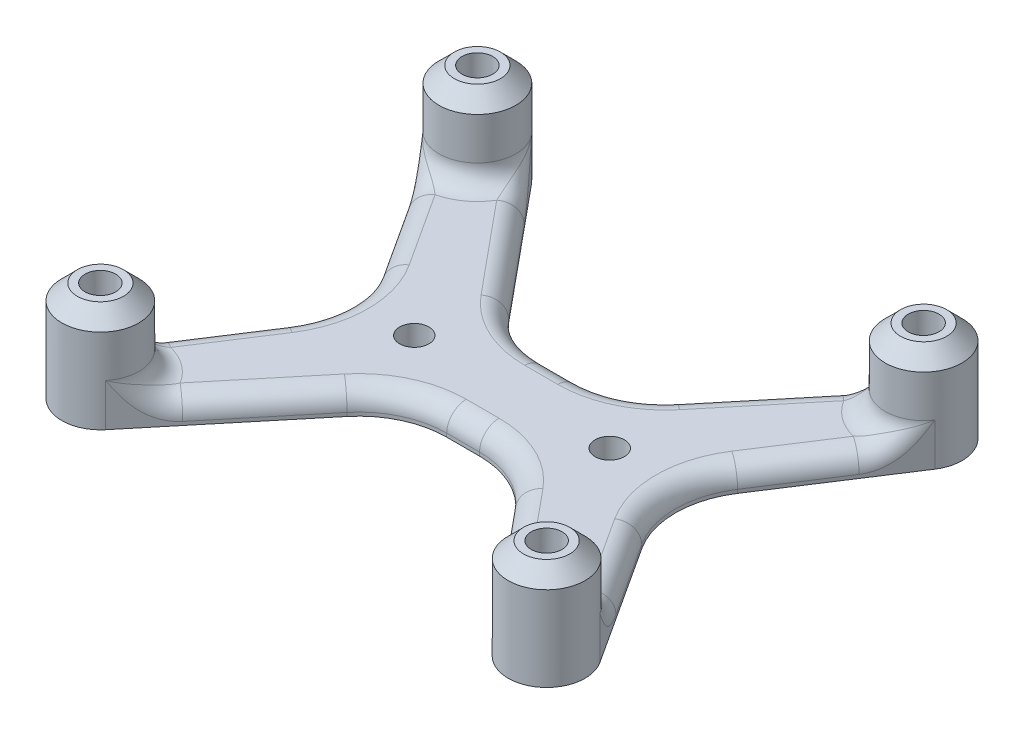
SolidWorks part; units mm, degrees
ref_plane "Front Plane" through (0, 0, 0) normal (0, 0, 1) x (1, 0, 0)
ref_plane "Top Plane" through (0, 0, 0) normal (0, 1, 0) x (1, 0, 0)
ref_plane "Right Plane" through (0, 0, 0) normal (1, 0, 0) x (0, 0, -1)
sketch "Sketch1" plane through (0, 0, 0) normal (0, 1, 0) x (1, 0, 0)
  line L0 (-7.5163, 6.35) -> (7.5163, 6.35)
  line L1 (-29, -24.5) -> (29, -24.5) construction
  line L2 (-29, -24.5) -> (-29, 24.5) construction
  line L3 (-29, 24.5) -> (29, 24.5) construction
  line L4 (29, -24.5) -> (29, 24.5) construction
  line L5 (-29, -24.5) -> (29, 24.5) construction
  line L6 (-29, 24.5) -> (29, -24.5) construction
  line L7 (-19.05, -6.35) -> (19.05, -6.35) construction
  line L8 (-19.05, -6.35) -> (-19.05, 6.35) construction
  line L9 (-19.05, 6.35) -> (19.05, 6.35) construction
  line L10 (19.05, -6.35) -> (19.05, 6.35) construction
  line L11 (-19.05, -6.35) -> (19.05, 6.35) construction
  line L12 (-19.05, 6.35) -> (19.05, -6.35) construction
  line L13 (7.5163, 6.35) -> (25.1456, 27.6849)
  line L14 (19.05, 0) -> (33.1932, 21.7766)
  line L15 (19.05, 0) -> (33.1932, -21.7766)
  line L16 (25.1456, -27.6849) -> (7.5163, -6.35)
  line L17 (7.5163, -6.35) -> (-7.5163, -6.35)
  line L18 (-7.5163, -6.35) -> (-25.1456, -27.6849)
  line L19 (-19.05, 0) -> (-33.1932, -21.7766)
  line L20 (-19.05, 0) -> (-33.1932, 21.7766)
  line L21 (-25.1456, 27.6849) -> (-7.5163, 6.35)
  circle A0 centre (-29, -24.5) radius 5
  circle A1 centre (29, -24.5) radius 5
  circle A2 centre (29, 24.5) radius 5
  circle A3 centre (-29, 24.5) radius 5
  point P0 (0, 0)
  point P6 (0, 0)
  dimension "D5" = 10
  dimension "D6" = 10
  dimension "D7" = 10
  dimension "D8" = 10
  dimension "D1" = 12.7
  dimension "D2" = 38.1
  dimension "D3" = 58
  dimension "D4" = 49
extrude "Boss-Extrude1" add sketch "Sketch1" along normal blind 3 contours A0 | A3 L20 L19 A0 L18 L17 L16 A1 L15 L14 A2 L13 L0 L21 | A3 | A2 | A1 region at (0, 0, 0) region at (-29, 0, -24.5) region at (29, 0, -24.5) region at (-29, 0, 24.5) region at (29, 0, 24.5)
sketch "Sketch2" plane through (0, 3, 0) normal (0, 1, 0) x (1, 0, 0)
  circle A0 centre (-29, -24.5) radius 5
  circle A1 centre (29, -24.5) radius 5
  circle A2 centre (29, 24.5) radius 5
  circle A3 centre (-29, 24.5) radius 5
extrude "Boss-Extrude2" add sketch "Sketch2" along normal blind 10
sketch "Sketch3" plane through (0, 13, 0) normal (0, 1, 0) x (1, 0, 0)
  circle A0 centre (-29, -24.5) radius 2
  circle A1 centre (-29, 24.5) radius 2
  circle A2 centre (29, 24.5) radius 2
  circle A3 centre (29, -24.5) radius 2
  dimension "D1" = 4
  dimension "D2" = 4
  dimension "D3" = 4
  dimension "D4" = 4
extrude "Cut-Extrude1" cut sketch "Sketch3" against normal blind 4.8
fillet "Fillet2" radius 11.43 4 edges at (7.5163, 1.5, -6.35) (-7.5163, 1.5, -6.35) (7.5163, 1.5, 6.35) (-7.5163, 1.5, 6.35)
fillet "Fillet3" radius 11.43 2 edges at (-19.05, 1.5, 0) (19.05, 1.5, 0)
fillet "Fillet4" radius 2.54 4 edges at (-26.041, 3, 20.4696) (26.041, 3, 20.4696) (26.041, 3, -20.4696) (-26.041, 3, -20.4696)
fillet "Fillet5" radius 2.54 24 edges at (31.0686, 3.3005, 18.5052) (26.6063, 3, 11.6346) (31.0686, 3.3005, -18.5052) (26.6063, 3, -11.6346) (-22.6609, 3.3005, 24.6779) (-16.2478, 3, 16.9168) (-7.0034, 3, 7.4392) (0, 3, 6.35) (22.6609, 3.3005, 24.6779) (16.2478, 3, 16.9168) (-31.0686, 3.3005, -18.5052) (-26.6063, 3, -11.6346) (-31.0686, 3.3005, 18.5052) (-26.6063, 3, 11.6346) (-22.6609, 3.3005, -24.6779) (-16.2478, 3, -16.9168) (-7.0034, 3, -7.4392) (0, 3, -6.35) (7.0034, 3, -7.4392) (22.6609, 3.3005, -24.6779) (21.2491, 3, 0) (7.0034, 3, 7.4392) (-21.2491, 3, 0) (16.2478, 3, -16.9168)
sketch "Sketch4" plane through (0, 3, 0) normal (0, 1, 0) x (1, 0, 0)
  circle A0 centre (-12.7, 0) radius 1.905
  circle A1 centre (12.7, 0) radius 1.905
  dimension "D1" = 3.81
  dimension "D3" = 3.81
  dimension "D2" = 12.7
  dimension "D4" = 12.7
extrude "Cut-Extrude2" cut sketch "Sketch4" against normal through all
chamfer "Chamfer1" distance 2 angle 45 4 edges at (-29, 13, 29.5) (-29, 13, -19.5) (29, 13, -19.5) (29, 13, 29.5)
sketch "Sketch5" plane through (0, 8.2, 0) normal (0, 1, 0) x (1, 0, 0)
  circle A0 centre (-29, -24.5) radius 1.6
  dimension "D1" = 3.2
extrude "Cut-Extrude3" cut sketch "Sketch5" against normal through all
mirror "Mirror1" about plane through (0, 0, 0) normal (1, 0, 0) of "Cut-Extrude3" second plane through (0, 0, 0) second plane normal (0, 0, 1)
